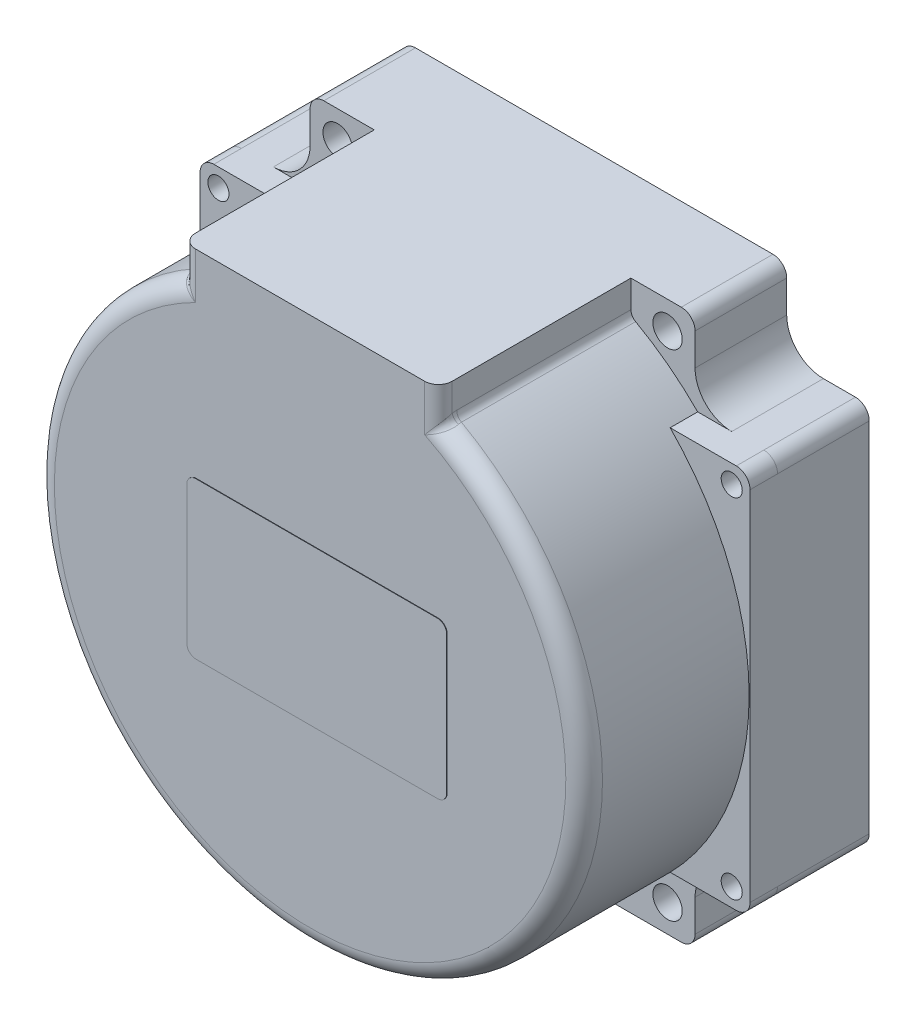
SolidWorks part; units mm, degrees
material "6061 Alloy"
ref_plane "Front Plane" through (0, 0, 0) normal (0, 0, 1) x (1, 0, 0)
ref_plane "Top Plane" through (0, 0, 0) normal (0, 1, 0) x (1, 0, 0)
ref_plane "Right Plane" through (0, 0, 0) normal (1, 0, 0) x (0, 0, -1)
sketch "Sketch1" plane through (0, 0, 0) normal (0, 0, 1) x (1, 0, 0)
  line L1 (9, 0) -> (51, 0)
  line L2 (0, 9) -> (0, 51)
  line L3 (9, 60) -> (51, 60)
  line L4 (60, 9) -> (60, 51)
  line L6 (51, 60) -> (51, 51)
  line L7 (51, 51) -> (60, 51)
  line L11 (0, 51) -> (9, 51)
  line L12 (9, 60) -> (9, 51)
  line L13 (0, 9) -> (9, 9)
  line L16 (9, 9) -> (9, 0)
  line L19 (60, 9) -> (51, 9)
  line L20 (51, 0) -> (51, 9)
  dimension "D1" = 60
  dimension "D2" = 60
  dimension "D3" = 9
  dimension "D4" = 9
  dimension "D5" = 9
  dimension "D6" = 9
  dimension "D7" = 9
  dimension "D8" = 9
  dimension "D9" = 9
  dimension "D10" = 9
extrude "Boss-Extrude1" add sketch "Sketch1" along normal blind 31
fillet "Fillet1" radius 4 1 edges at (51, 51, 15.5)
fillet "Fillet2" radius 4 3 edges at (9, 51, 15.5) (9, 9, 15.5) (51, 9, 15.5)
fillet "Fillet3" radius 1.5 8 edges at (9, 60, 15.5) (0, 51, 15.5) (0, 9, 15.5) (9, 0, 15.5) (51, 0, 15.5) (60, 9, 15.5) (60, 51, 15.5) (51, 60, 15.5)
sketch "Sketch2" plane through (0, 0, 31) normal (0, 0, 1) x (1, 0, 0)
  line L0 (30, 66.074) -> (30, -6.5173) construction
  line L1 (0, 49.5) -> (0, 10.5) construction
  line L2 (49.5, 60) -> (10.5, 60) construction
  line L4 (16, 60) -> (44, 60)
  line L5 (16, 60) -> (16, 56.4199)
  line L7 (44, 60) -> (44, 56.4199)
  arc A0 (16, 56.4199) -> (44, 56.4199) centre (30, 30) ccw
  circle A1 centre (30, 30) radius 55.1009
  dimension "D2" = 30
  dimension "D1" = 30
  dimension "D3" = 14
  dimension "D4" = 14
extrude "Cut-Extrude1" cut sketch "Sketch2" against normal blind 21
fillet "Fillet4" radius 2 1 edges at (30, 0.1, 31)
fillet "Fillet5" radius 1.5 1 edges at (16, 57.0666, 31)
fillet "Fillet6" radius 1.5 1 edges at (44, 57.0666, 31)
fillet "Fillet7" radius 1 3 edges at (43.6823, 55.9151, 30.4231) (44, 56.4199, 19.5)
fillet "Fillet8" radius 1 3 edges at (16.3177, 55.9151, 30.4231) (16, 56.4199, 19.5)
sketch "Sketch4" plane through (0, 0, 10) normal (0, 0, 1) x (1, 0, 0)
  line L0 (0, 51) -> (0, 9)
  line L1 (0, 51) -> (8.716, 51)
  line L2 (0, 9) -> (8.716, 9)
  line L3 (1.5, 9) -> (5, 9) construction
  line L4 (5, 51) -> (1.5, 51) construction
  line L5 (30, 30) -> (30, 72.5572) construction
  line L6 (60, 9) -> (51.284, 9)
  line L7 (60, 51) -> (51.284, 51)
  line L8 (60, 51) -> (60, 9)
  arc A0 (8.716, 51) -> (8.716, 9) centre (30, 30) ccw
  arc A2 (51.284, 9) -> (51.284, 51) centre (30, 30) ccw
extrude "Boss-Extrude2" add sketch "Sketch4" along normal blind 3
fillet "Fillet9" radius 1.5 1 edges at (0, 51, 11.5)
fillet "Fillet10" radius 1.5 3 edges at (60, 51, 11.5) (60, 9, 11.5) (0, 9, 11.5)
hole_wizard "Ø2.3 (2.3) Diameter Hole1" positions "Sketch6" profile "Sketch5" hole size "Ø2.3" standard "ANSI Metric" end condition through all
sketch "Sketch6" plane through (0, 0, 13) normal (0, 0, 1) x (1, 0, 0)
  line L0 (8.716, 51) -> (1.5, 51) construction
  line L1 (0, 49.5) -> (0, 10.5) construction
  point P0 (2, 49)
  dimension "D1" = 2
  dimension "D2" = 2
sketch "Sketch5" plane through (2, 49, 13) normal (1, 0, 0) x (0, -1, 0)
  line L0 (0, 0) -> (0, 13)
  line L1 (0, 13) -> (1.15, 13)
  line L2 (1.15, 13) -> (1.15, 0)
  line L5 (1.15, 0) -> (0, 0)
  line L11 (0, -6.35) -> (0, 107.95) construction
  dimension "Thru Hole Dia." = 2.3
  dimension "Thru Hole Depth" = 13
pattern_linear "LPattern1" count 2 spacing 56 along (1, 0, 0) of "Ø2.3 (2.3) Diameter Hole1"
pattern_linear "LPattern2" count 2 spacing 38 along (0, -1, 0) of "LPattern1", "Ø2.3 (2.3) Diameter Hole1"
hole_wizard "Ø3.2 (3.2) Diameter Hole1" positions "Sketch8" profile "Sketch7" hole size "Ø3.2" standard "ANSI Metric" end condition through all
sketch "Sketch8" plane through (0, 0, 10) normal (0, 0, 1) x (1, 0, 0)
  line L0 (16, 60) -> (10.5, 60) construction
  line L1 (9, 58.5) -> (9, 55) construction
  point P0 (12, 57)
  dimension "D1" = 3
  dimension "D2" = 3
sketch "Sketch7" plane through (12, 57, 10) normal (1, 0, 0) x (0, -1, 0)
  line L0 (0, 0) -> (0, 10)
  line L1 (0, 10) -> (1.6, 10)
  line L2 (1.6, 10) -> (1.6, 0)
  line L5 (1.6, 0) -> (0, 0)
  line L11 (0, -6.35) -> (0, 107.95) construction
  dimension "Thru Hole Dia." = 3.2
  dimension "Thru Hole Depth" = 10
pattern_linear "LPattern3" count 2 spacing 36 along (1, 0, 0) of "Ø3.2 (3.2) Diameter Hole1"
pattern_linear "LPattern4" count 2 spacing 54 along (0, -1, 0) of "LPattern3", "Ø3.2 (3.2) Diameter Hole1"
sketch "Sketch9" plane through (0, 0, 31) normal (0, 0, 1) x (1, 0, 0)
  line L1 (17.6019, 38.3619) -> (43.9548, 38.3619)
  line L2 (16.6019, 37.3619) -> (16.6019, 22.3154)
  line L3 (17.6019, 21.3154) -> (43.9548, 21.3154)
  line L4 (44.9548, 37.3619) -> (44.9548, 22.3154)
  arc A0 (16.6019, 22.3154) -> (17.6019, 21.3154) centre (17.6019, 22.3154) ccw
  arc A1 (43.9548, 21.3154) -> (44.9548, 22.3154) centre (43.9548, 22.3154) ccw
  arc A2 (43.9548, 38.3619) -> (44.9548, 37.3619) centre (43.9548, 37.3619) cw
  arc A3 (16.6019, 37.3619) -> (17.6019, 38.3619) centre (17.6019, 37.3619) cw
  dimension "D1" = 1
extrude "Boss-Extrude3" add sketch "Sketch9" along normal blind 0.05
sketch "Sketch10" plane through (0, 0, 0) normal (0, 0, -1) x (-1, 0, 0)
  line L0 (-60, 30) -> (0, 30) construction
  line L1 (-60, 10.5) -> (-60, 49.5) construction
  line L2 (0, 49.5) -> (0, 10.5) construction
  circle A0 centre (-30, 30) radius 25
extrude "Cut-Extrude2" cut sketch "Sketch10" against normal blind 25
scale "Scale1" scale about centroid uniform scaling yes scale factor 2.3
